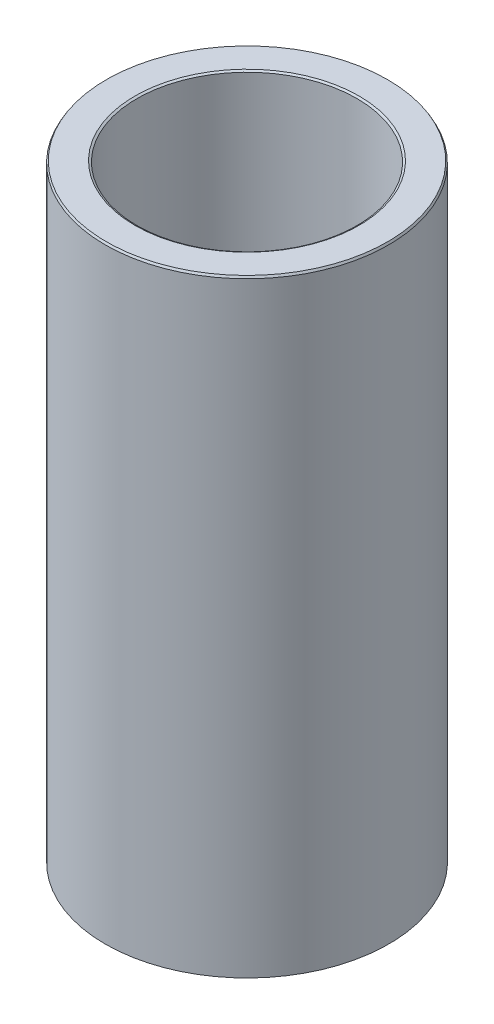
SolidWorks part; units mm, degrees
ref_plane "Front Plane" through (0, 0, 0) normal (0, 0, 1) x (1, 0, 0)
ref_plane "Top Plane" through (0, 0, 0) normal (0, 1, 0) x (1, 0, 0)
ref_plane "Right Plane" through (0, 0, 0) normal (1, 0, 0) x (0, 0, -1)
sketch "Sketch1" plane through (0, 0, 0) normal (0, 1, 0) x (1, 0, 0)
  circle A0 centre (0, 0) radius 15
  dimension "SLEEVE_OD" = 30
extrude "Boss-Extrude1" add sketch "Sketch1" along normal blind 64.4296
sketch "Sketch2" plane through (0, 0, 0) normal (0, 1, 0) x (1, 0, 0)
  circle A0 centre (0, 0) radius 11.6459
  dimension "BORE_D" = 23.2917
extrude "Cut-Extrude1" cut sketch "Sketch2" along normal through all
chamfer "Chamfer1" distance 0.2165 angle 30 4 edges at (0, 64.4296, 11.6459) (0, 0, 11.6459) (0, 0, 15) (0, 64.4296, 15) first distance on face at (0, 64.4296, 11.6459) first distance on face at (0, 0, 11.6459) first distance on face at (0, 64.4296, 15)
